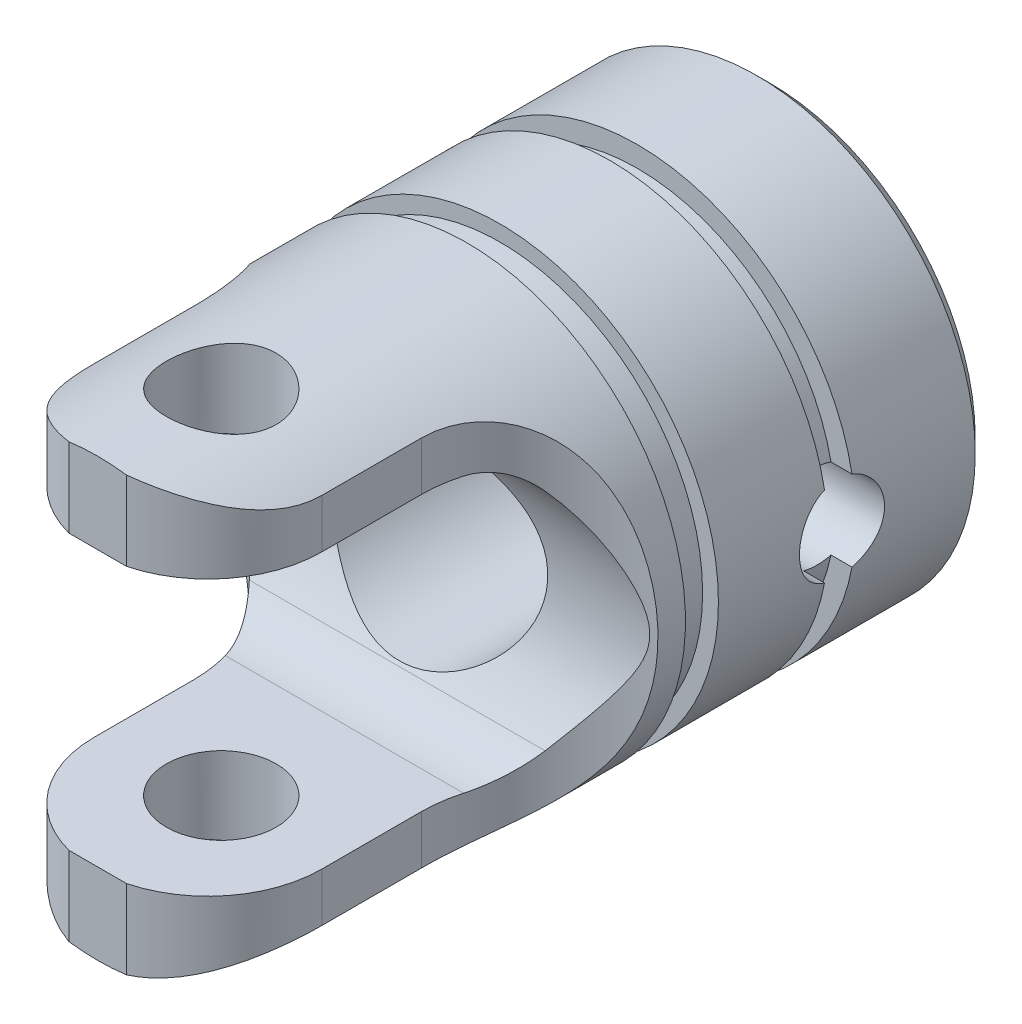
SolidWorks part; units mm, degrees
material "AISI 1020"
ref_plane "Front Plane" through (0, 0, 0) normal (0, 0, 1) x (1, 0, 0)
ref_plane "Top Plane" through (0, 0, 0) normal (0, 1, 0) x (1, 0, 0)
ref_plane "Right Plane" through (0, 0, 0) normal (1, 0, 0) x (0, 0, -1)
sketch "Sketch1" plane through (0, 0, 0) normal (0, 0, 1) x (1, 0, 0)
  circle A1 centre (0, 0) radius 15.9
  dimension "D1" = 31.8
extrude "Boss-Extrude1" add sketch "Sketch1" along normal blind 49 contours A1
sketch "Sketch2" plane through (0, 0, 0) normal (0, 0, 1) x (1, 0, 0)
  circle A0 centre (0, 0) radius 8
extrude "Cut-Extrude1" cut sketch "Sketch2" along normal blind 49
sketch "Sketch3" plane through (0, 0, 0) normal (1, 0, 0) x (0, 0, -1)
  line L3 (0, 17.545) -> (0, -17.545) construction
  circle A1 centre (-10.7, 0) radius 3.1
  dimension "D1" = 10.7
  dimension "D2" = 6.2
extrude "Cut-Extrude2" cut sketch "Sketch3" against normal through all both and the other way through all
sketch "Sketch4" plane through (0, 0, 0) normal (0, 1, 0) x (1, 0, 0)
  line L0 (15.9, -7.6) -> (15.9, -13.8) construction
  line L2 (14.4, -9.7) -> (17.4, -9.7)
  line L3 (14.4, -9.7) -> (14.4, -11.7)
  line L4 (14.4, -11.7) -> (17.4, -11.7)
  line L5 (17.4, -9.7) -> (17.4, -11.7)
  line L6 (14.4, -9.7) -> (17.4, -11.7) construction
  line L7 (14.4, -11.7) -> (17.4, -9.7) construction
  point P4 (15.9, -10.7)
  point P9 (14.4, -10.7)
  dimension "D1" = 1
  dimension "D2" = 1.5
sketch "Sketch6" plane through (0, 0, 0) normal (0, 1, 0) x (1, 0, 0)
  line L0 (0, -49) -> (0, 0) construction
  line L1 (-15.9, -49) -> (15.9, -49) construction
  line L4 (14.4, -9.7) -> (17.4, -9.7)
  line L5 (14.4, -9.7) -> (14.4, -11.7)
  line L6 (14.4, -11.7) -> (17.4, -11.7)
  line L7 (17.4, -9.7) -> (17.4, -11.7)
  line L8 (14.4, -9.7) -> (17.4, -11.7) construction
  line L9 (14.4, -11.7) -> (17.4, -9.7) construction
  point P7 (15.9, -10.7)
revolve "Cut-Revolve2" cut sketch "Sketch6" angle 360 about L0
sketch "Sketch7" plane through (0, 0, 0) normal (0, 1, 0) x (1, 0, 0)
  line L0 (15.9, -49) -> (15.9, -13.8) construction
  line L1 (17.05, -19.7) -> (14.75, -19.7)
  line L2 (17.05, -19.7) -> (17.05, -22.1)
  line L3 (17.05, -22.1) -> (14.75, -22.1)
  line L4 (14.75, -19.7) -> (14.75, -22.1)
  line L5 (17.05, -19.7) -> (14.75, -22.1) construction
  line L6 (17.05, -22.1) -> (14.75, -19.7) construction
  line L7 (14.4, -11.7) -> (17.4, -11.7) construction
  line L9 (0, 0) -> (0, -49) construction
  line L10 (-15.9, -49) -> (15.9, -49) construction
  point P0 (15.9, -20.9)
  point P9 (17.05, -20.9)
  dimension "D1" = 8
  dimension "D2" = 2.4
  dimension "D3" = 2.3
revolve "Cut-Revolve3" cut sketch "Sketch7" angle 360 about L9
sketch "Sketch8" plane through (0, 0, 0) normal (0, 1, 0) x (1, 0, 0)
  line L0 (15.9, -24.1) -> (15.9, -43.3622)
  line L1 (15.9, -49) -> (15.9, -22.1) construction
  line L4 (8.3, -40.9701) -> (8.3, -33.7311)
  line L5 (-15.9, -24.1) -> (-15.9, -50.3727)
  line L6 (-15.9, -50.3727) -> (15.9, -50.3727)
  line L7 (15.9, -50.3727) -> (15.9, -43.3622)
  line L8 (-8.3, -40.9701) -> (-8.3, -33.7311)
  arc A0 (15.9, -24.1) -> (8.3, -33.7311) centre (18.2025, -33.7311) ccw
  arc A1 (-15.9, -24.1) -> (-8.3, -33.7311) centre (-18.2025, -33.7311) cw
  arc A2 (-8.3, -40.9701) -> (8.3, -40.9701) centre (0, -40.9701) ccw
extrude "Cut-Extrude3" cut sketch "Sketch8" against normal through all both and the other way through all
sketch "Sketch9" plane through (0, 0, 0) normal (1, 0, 0) x (0, 0, -1)
  line L0 (12, 3.5063) -> (12, -7.637)
  line L1 (-49.0568, 10) -> (-49.0251, -10)
  line L2 (-49.0568, 10) -> (-29.0568, 10)
  line L3 (-49.0251, -10) -> (-29.0251, -10)
  arc A1 (-29.0251, -10) -> (-29.0568, 10) centre (-37.0158, -0.0126) ccw
  point P5 (-49.0409, 0)
  dimension "D4" = 12.7906
  dimension "D1" = 20
  dimension "D2" = 20
  dimension "D3" = 20
extrude "Cut-Extrude4" cut sketch "Sketch9" against normal through all both and the other way through all contours L3 A1 L2 L1 region at (0, 0.0004, 37.3228)
chamfer "Chamfer1" distance 1 angle 45 2 edges at (8, 0, 0) (15.9, 0, 0)
sketch "Sketch10" plane through (0, -10, 0) normal (0, 1, 0) x (1, 0, 0)
  line L0 (0, -17.49) -> (0, 17.49) construction
  line L1 (-2.1, -49) -> (2.1, -49) construction
  circle A0 centre (0, -40) radius 4
  dimension "D1" = 8
  dimension "D2" = 9
extrude "Cut-Extrude5" cut sketch "Sketch10" against normal through all both and the other way through all
fillet "Fillet2" radius 5 2 edges at (0, -10, 29.0251) (0, 10, 29.0568)
sketch "Sketch11" plane through (0, 0, 0) normal (0, 1, 0) x (1, 0, 0)
  line L0 (15.9, -10.7) -> (-15.9996, -10.7) construction
